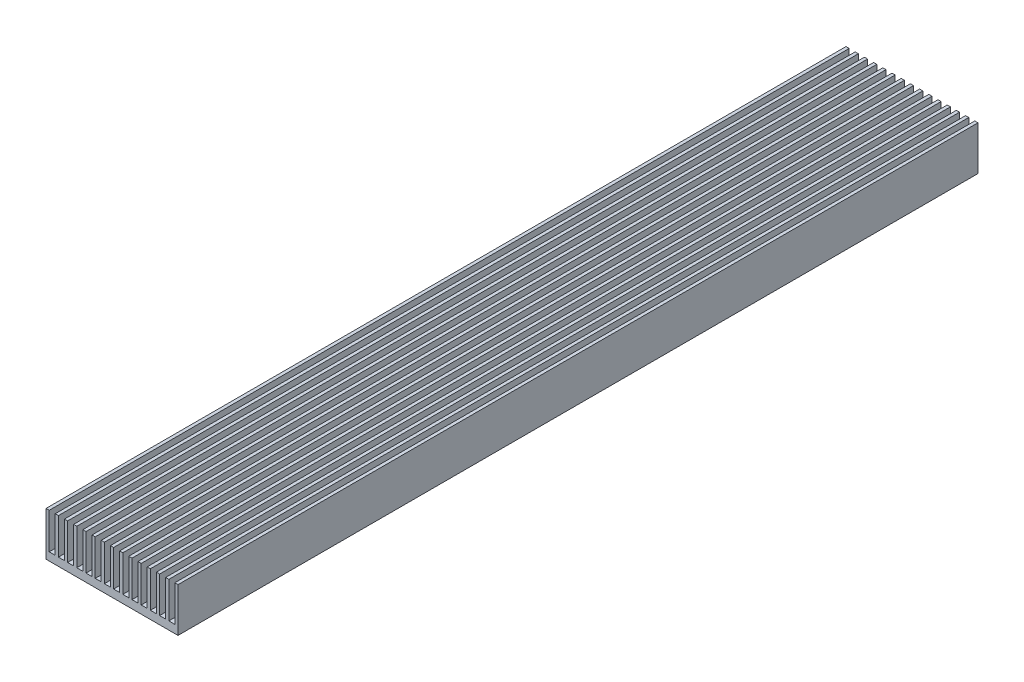
SolidWorks part; units mm, degrees
ref_plane "Ön Düzlem" through (0, 0, 0) normal (0, 0, 1) x (1, 0, 0)
ref_plane "Üst Düzlem" through (0, 0, 0) normal (0, 1, 0) x (1, 0, 0)
ref_plane "Sağ Düzlem" through (0, 0, 0) normal (1, 0, 0) x (0, 0, -1)
sketch "Sketch1" plane through (0, 0, 0) normal (0, 0, 1) x (1, 0, 0)
  line L0 (11.5, 10) -> (11.5, 55)
  line L1 (0, 0) -> (165, 0)
  line L2 (0, 0) -> (0, 10)
  line L3 (4, 10) -> (11.5, 10)
  line L4 (165, 0) -> (165, 10)
  line L6 (0, 10) -> (0, 55)
  line L7 (0, 55) -> (4, 55)
  line L8 (4, 10) -> (4, 55)
  line L10 (15.5, 10) -> (15.5, 55)
  line L11 (11.5, 55) -> (15.5, 55)
  line L12 (23, 10) -> (23, 55)
  line L14 (27, 10) -> (27, 55)
  line L15 (23, 55) -> (27, 55)
  line L16 (34.5, 10) -> (34.5, 55)
  line L18 (38.5, 10) -> (38.5, 55)
  line L19 (34.5, 55) -> (38.5, 55)
  line L20 (46, 10) -> (46, 55)
  line L22 (50, 10) -> (50, 55)
  line L23 (46, 55) -> (50, 55)
  line L24 (57.5, 10) -> (57.5, 55)
  line L26 (61.5, 10) -> (61.5, 55)
  line L27 (57.5, 55) -> (61.5, 55)
  line L28 (69, 10) -> (69, 55)
  line L30 (73, 10) -> (73, 55)
  line L31 (69, 55) -> (73, 55)
  line L32 (80.5, 10) -> (80.5, 55)
  line L34 (84.5, 10) -> (84.5, 55)
  line L35 (80.5, 55) -> (84.5, 55)
  line L36 (92, 10) -> (92, 55)
  line L38 (96, 10) -> (96, 55)
  line L39 (92, 55) -> (96, 55)
  line L40 (103.5, 10) -> (103.5, 55)
  line L42 (107.5, 10) -> (107.5, 55)
  line L43 (103.5, 55) -> (107.5, 55)
  line L44 (115, 10) -> (115, 55)
  line L46 (119, 10) -> (119, 55)
  line L47 (115, 55) -> (119, 55)
  line L48 (126.5, 10) -> (126.5, 55)
  line L50 (130.5, 10) -> (130.5, 55)
  line L51 (126.5, 55) -> (130.5, 55)
  line L52 (138, 10) -> (138, 55)
  line L54 (142, 10) -> (142, 55)
  line L55 (138, 55) -> (142, 55)
  line L56 (149.5, 10) -> (149.5, 55)
  line L58 (153.5, 10) -> (153.5, 55)
  line L59 (149.5, 55) -> (153.5, 55)
  line L60 (161, 10) -> (161, 55)
  line L62 (165, 10) -> (165, 55)
  line L63 (161, 55) -> (165, 55)
  line L78 (15.5, 10) -> (23, 10)
  line L79 (27, 10) -> (34.5, 10)
  line L80 (38.5, 10) -> (46, 10)
  line L81 (50, 10) -> (57.5, 10)
  line L82 (61.5, 10) -> (69, 10)
  line L83 (73, 10) -> (80.5, 10)
  line L84 (84.5, 10) -> (92, 10)
  line L85 (96, 10) -> (103.5, 10)
  line L86 (107.5, 10) -> (115, 10)
  line L87 (119, 10) -> (126.5, 10)
  line L88 (130.5, 10) -> (138, 10)
  line L89 (142, 10) -> (149.5, 10)
  line L90 (153.5, 10) -> (161, 10)
  point P8 (0, 0)
  dimension "D1" = 165
  dimension "D2" = 10
  dimension "D3" = 45
  dimension "D4" = 4
  dimension "D5" = 15
extrude "Boss-Extrude1" add sketch "Sketch1" along normal blind 1000 contours L90 L58 L59 L56 L89 L54 L55 L52 L88 L50 L51 L48 L87 L46 L47 L44 L86 L42 L43 L40 L85 L38 L39 L36 L84 L34 L35 L32 L83 L30 L31 L28 L82 L26 L27 L24 L81 L22 L23 L20 L80 L18 L19 L16 L79 L14 L15 L12 L78 L10 L11 region at (82.5, 22.069, 0)
